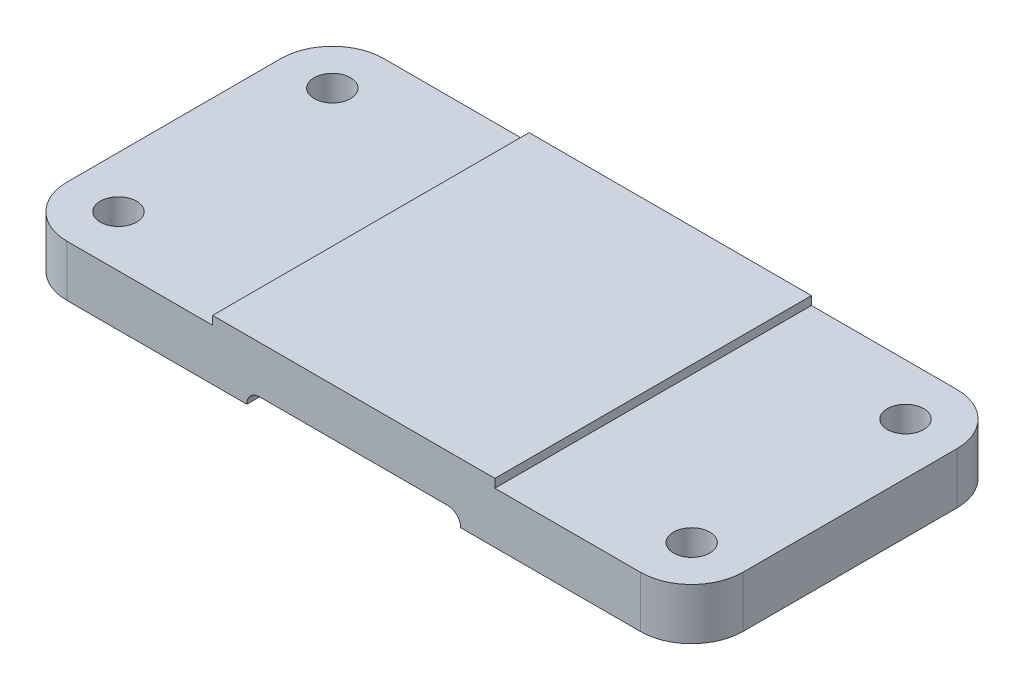
SolidWorks part; units mm, degrees
material "Gray Cast Iron"
ref_plane "Front Plane" through (0, 0, 0) normal (0, 0, 1) x (1, 0, 0)
ref_plane "Top Plane" through (0, 0, 0) normal (0, 1, 0) x (1, 0, 0)
ref_plane "Right Plane" through (0, 0, 0) normal (1, 0, 0) x (0, 0, -1)
sketch "Sketch2" plane through (0, 0, 0) normal (0, 1, 0) x (1, 0, 0)
  line L0 (46, 74) -> (46, 0)
  line L1 (12, 0) -> (146, 0)
  line L2 (0, 12) -> (0, 62)
  line L3 (12, 74) -> (146, 74)
  line L4 (158, 12) -> (158, 62)
  line L5 (112, 0) -> (112, 74)
  line L6 (54, 74) -> (54, 0) construction
  line L7 (104, 0) -> (104, 74) construction
  line L8 (104, 0) -> (104, 74)
  line L9 (54, 74) -> (54, 0)
  arc A0 (0, 62) -> (12, 74) centre (12, 62) cw
  arc A1 (146, 74) -> (158, 62) centre (146, 62) cw
  arc A2 (146, 0) -> (158, 12) centre (146, 12) ccw
  arc A3 (12, 0) -> (0, 12) centre (12, 12) cw
  point P13 (0, 0)
  dimension "D3" = 12
  dimension "D1" = 158
  dimension "D2" = 74
  dimension "D4" = 50
  dimension "D5" = 134
  dimension "D10" = 46
  dimension "D11" = 46
  dimension "D12" = 54
  dimension "D13" = 54
extrude "Boss-Extrude2" add sketch "Sketch2" along normal blind 12
sketch3d "3DSketch2"
  line L0 (12, 12, 0) -> (146, 12, 0) construction
  line L1 (158, 12, -12) -> (158, 12, -62) construction
  line L2 (112, 12, 0) -> (112, 12, -74)
  line L3 (12, 12, -74) -> (146, 12, -74) construction
  line L4 (46, 12, 0) -> (46, 12, -74)
  line L5 (158, 12, -12) -> (158, 12, -62) construction
  line L6 (158, 12, -62) -> (0, 12, -62) construction
  line L7 (0, 12, -62) -> (0, 12, -12) construction
  line L8 (0, 12, -12) -> (158, 12, -12) construction
  line L9 (112, 12, 0) -> (46, 12, 0)
  line L10 (46, 12, -74) -> (112, 12, -74)
  dimension "D1" = 46
  dimension "D2" = 46
extrude "Boss-Extrude3" add sketch "3DSketch2" along direction (0, 1, 0) on the side against the normal blind 2 contours L2 L10 L4 L9
sketch3d "3DSketch3"
  line L0 (12, 0, -74) -> (146, 0, -74) construction
  line L1 (0, 0, -12) -> (0, 0, -62) construction
  line L2 (158, 0, -62) -> (158, 0, -12) construction
  line L3 (158, 0, -12) -> (0, 0, -12) construction
  line L4 (0, 0, -12) -> (0, 0, -62) construction
  line L5 (0, 0, -62) -> (158, 0, -62) construction
  line L6 (104, 0, -74) -> (104, 0, 0)
  line L7 (12, 0, 0) -> (146, 0, 0) construction
  line L8 (104, 0, 0) -> (54, 0, 0)
  line L9 (54, 0, 0) -> (54, 0, -74)
  line L10 (54, 0, -74) -> (104, 0, -74)
  dimension "D1" = 54
  dimension "D2" = 54
extrude "Cut-Extrude1" cut sketch "3DSketch3" along direction (0, 1, 0) on the side against the normal blind 3
fillet "Fillet1" radius 3 2 edges
sketch3d "3DSketch6"
  line L0 (12, 12, -74) -> (46, 12, -74) construction
  line L1 (0, 12, -12) -> (0, 12, -62) construction
  line L2 (46, 12, -12) -> (46, 12, -62)
  line L3 (12, 12, -62) -> (146, 12, -62)
  line L4 (12, 12, -62) -> (12, 12, -12)
  line L5 (12, 12, -12) -> (146, 12, -12)
  line L6 (146, 12, -62) -> (146, 12, -12)
  line L7 (46, 12, 0) -> (46, 12, -74) construction
  line L8 (12, 12, -74) -> (46, 12, -74)
  point P16 (12, 12, -12)
  point P17 (12, 12, -62)
  point P18 (146, 12, -12)
  point P19 (146, 12, -62)
  dimension "D1" = 50
  dimension "D2" = 134
  dimension "D3" = 34
  dimension "D4" = 12
hole_wizard "Tap Drill for M10x1.5 Tap1" positions "Sketch6" profile "Sketch5" hole size "M10x1.5" standard "ANSI Metric"
sketch "Sketch6" plane through (0, 12, 0) normal (0, 1, 0) x (1, 0, 0)
  point P0 (146, 12)
  point P3 (146, 62)
  point P6 (12, 12)
  point P9 (12, 62)
sketch "Sketch5" plane through (146, 12, -12) normal (1, 0, 0) x (0, 0, 1)
  line L0 (0, 0) -> (0, 16.8)
  line L1 (0, 16.8) -> (4.25, 12.55)
  line L2 (4.25, 12.55) -> (4.25, 0)
  line L5 (4.25, 0) -> (0, 0)
  line L10 (0, 16.8) -> (-4.25, 12.55) construction
  line L11 (0, -6.35) -> (0, 107.95) construction
  dimension "Hole Dia." = 8.5
  dimension "Hole Depth" = 12.55
  dimension "Drill Angle" = 90
